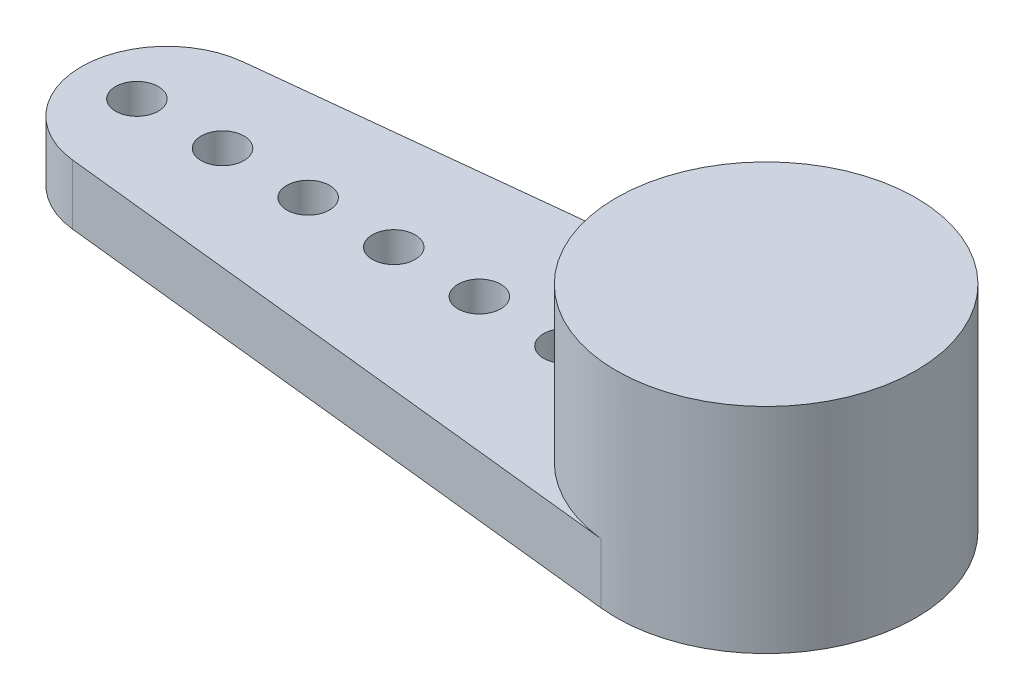
SolidWorks part; units mm, degrees
ref_plane "Plano frontal" through (0, 0, 0) normal (0, 0, 1) x (1, 0, 0)
ref_plane "Plano superior" through (0, 0, 0) normal (0, 1, 0) x (1, 0, 0)
ref_plane "Plano direito" through (0, 0, 0) normal (1, 0, 0) x (0, 0, -1)
sketch "Esboço1" plane through (0, 0, 0) normal (0, 1, 0) x (1, 0, 0)
  circle A0 centre (0, 0) radius 3.5
  dimension "D1" = 7
extrude "Ressalto-extrusão1" add sketch "Esboço1" along normal blind 5
sketch "Esboço2" plane through (0, 0, 0) normal (0, 1, 0) x (1, 0, 0)
  line L0 (0, 0) -> (-26.2962, 0) construction
  line L1 (-14.2143, 1.9885) -> (-0.375, 3.4799)
  line L2 (-14.2143, -1.9885) -> (-0.375, -3.4799)
  line L3 (-0.375, 3.4799) -> (-0.375, -3.4799)
  arc A0 (-14.2143, 1.9885) -> (-14.2143, -1.9885) centre (-14, 0) ccw
  circle A1 centre (0, 0) radius 3.5 construction
  point P3 (-16, 0)
  dimension "D1" = 4
  dimension "D2" = 16
extrude "Ressalto-extrusão2" add sketch "Esboço2" along normal blind 1.4
sketch "Esboço3" plane through (0, 0, 0) normal (0, 1, 0) x (1, 0, 0)
  circle A0 centre (-14.7, 0) radius 0.5
  arc A1 (-14.2143, 1.9885) -> (-14.2143, -1.9885) centre (-14, 0) ccw construction
  point P7 (-16, 0)
  dimension "D1" = 1
  dimension "D2" = 1.3
extrude "Corte-extrusão1" cut sketch "Esboço3" along normal through all
pattern_linear "Padrão linear1" count 6 spacing 2 along (1, 0, 0) of "Corte-extrusão1"
mirror "Espelhar1" [suppressed] about plane through (0, 0, 0) normal (1, 0, 0)
ref_axis "Eixo1" through (0, 5, 0) along (0, -1, 0)
sketch "Esboço5" plane through (0, 1.4, 0) normal (0, 1, 0) x (1, 0, 0)
  line L0 (-17.2354, 0) -> (17.2354, 0) construction
  circle A0 centre (-14.7, 0) radius 0.5 construction
  arc A1 (-0.375, 3.4799) -> (-0.375, -3.4799) centre (0, 0) ccw construction
  circle A2 centre (-12.7, 0) radius 0.5 construction
  circle A3 centre (-10.7, 0) radius 0.5 construction
  circle A4 centre (-8.7, 0) radius 0.5 construction
  circle A5 centre (0, 0) radius 3.5 construction
  circle A6 centre (-6.7, 0) radius 0.5 construction
  circle A7 centre (-4.7, 0) radius 0.5 construction
  dimension "D1" = 14.7
  dimension "D2" = 12.7
  dimension "D3" = 10.7
  dimension "D4" = 8.7
  dimension "D5" = 6.7
  dimension "D6" = 4.7
